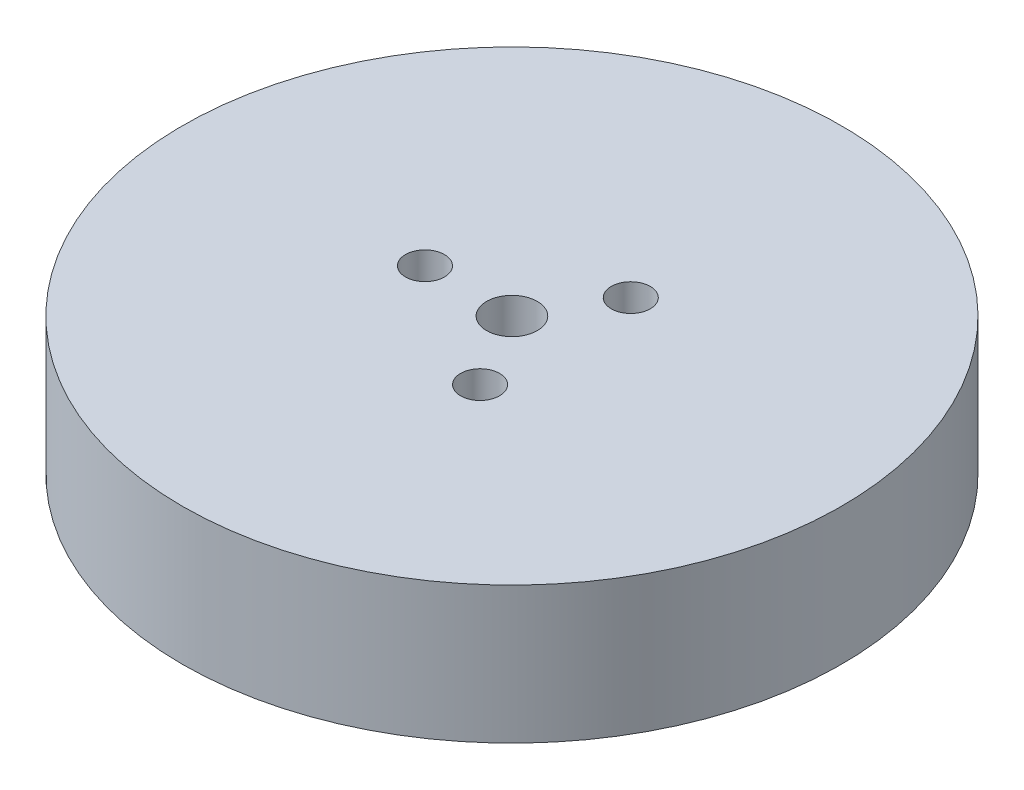
SolidWorks part; units mm, degrees
ref_plane "Front Plane" through (0, 0, 0) normal (0, 0, 1) x (1, 0, 0)
ref_plane "Top Plane" through (0, 0, 0) normal (0, 1, 0) x (1, 0, 0)
ref_plane "Right Plane" through (0, 0, 0) normal (1, 0, 0) x (0, 0, -1)
sketch "Sketch1" plane through (0, 0, 0) normal (0, 1, 0) x (1, 0, 0)
  circle A0 centre (0, 0) radius 65
  dimension "FLANGE_OD" = 130
extrude "Boss-Extrude1" add sketch "Sketch1" along normal blind 27
sketch "Sketch2" plane through (0, 0, 0) normal (0, 1, 0) x (1, 0, 0)
  circle A0 centre (0, 0) radius 5
  dimension "BORE_D" = 10
extrude "Cut-Extrude1" cut sketch "Sketch2" along normal through all
sketch "Sketch3" plane through (0, 27, 0) normal (0, 1, 0) x (1, 0, 0)
  circle A0 centre (0, 0) radius 17.1567 construction
  circle A1 centre (-17.1567, 0) radius 3.8418
  dimension "BOLT_D" = 7.6836
  dimension "BOLT_PCD" = 34.3134
extrude "Cut-Extrude2" cut sketch "Sketch3" against normal blind 21.5636
pattern_circular "CirPattern1" count 3 over 360 about axis through (0, 0, 0) along (0, 1, 0) of "Cut-Extrude2"
